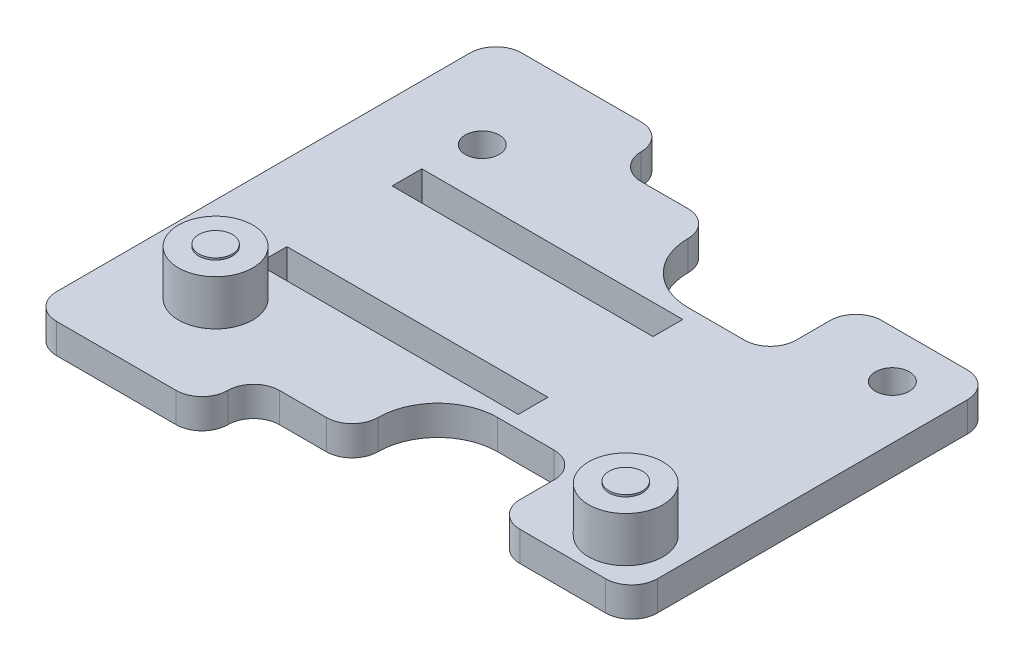
SolidWorks part; units mm, degrees
other "下垫片"
ref_plane "前视基准面" through (0, 0, 0) normal (0, 0, 1) x (1, 0, 0)
ref_plane "上视基准面" through (0, 0, 0) normal (0, 1, 0) x (1, 0, 0)
ref_plane "右视基准面" through (0, 0, 0) normal (1, 0, 0) x (0, 0, -1)
other "Configuration Table"
sketch "草图1" plane through (0, 0, 0) normal (0, 1, 0) x (1, 0, 0)
  line L0 (-89.3251, 0) -> (102.0425, 0) construction
  line L1 (0, 56.7239) -> (0, -62.578) construction
  line L2 (-33.2, -8.1375) -> (7.2, -8.1375)
  line L3 (-33.2, 12.7375) -> (7.2, 12.7375)
  line L4 (-33.2, 12.7375) -> (-33.2, 8.1375)
  line L5 (-33.2, 8.1375) -> (7.2, 8.1375)
  line L6 (7.2, 12.7375) -> (7.2, 8.1375)
  line L7 (-33.2, 12.7375) -> (7.2, 8.1375) construction
  line L8 (-33.2, 8.1375) -> (7.2, 12.7375) construction
  line L9 (7.2, -12.7375) -> (7.2, -8.1375)
  line L10 (-33.2, -12.7375) -> (7.2, -12.7375)
  line L11 (-33.2, -12.7375) -> (-33.2, -8.1375)
  line L14 (-3.25, -26.5375) -> (-3.25, -14.7375)
  line L15 (-3.25, -14.7375) -> (18.75, -14.7375)
  line L16 (18.75, -26.5375) -> (18.75, -14.7375)
  line L17 (-3.25, -26.5375) -> (18.75, -14.7375) construction
  line L18 (-3.25, -14.7375) -> (18.75, -26.5375) construction
  line L19 (-3.25, 14.7375) -> (18.75, 14.7375)
  line L20 (18.75, 26.5375) -> (18.75, 14.7375)
  line L22 (-3.25, 26.5375) -> (-3.25, 14.7375)
  line L23 (-3.25, 29.8695) -> (18.75, 29.8695)
  line L25 (-3.25, -26.5375) -> (-3.25, -29.8695)
  line L26 (-3.25, -29.8695) -> (18.75, -29.8695)
  line L27 (18.75, -26.5375) -> (18.75, -29.8695)
  line L28 (18.75, 26.5375) -> (18.75, 29.8695)
  line L30 (-3.25, 26.5375) -> (-3.25, 29.8695)
  circle A0 centre (-31.75, 20.6375) radius 2.625
  circle A4 centre (31.75, 20.6375) radius 2.625
  circle A5 centre (31.75, -20.6375) radius 2.625
  circle A6 centre (-31.75, -20.6375) radius 2.625
  point P13 (-13, 10.4375)
  point P22 (7.75, -20.6375)
  point P35 (-13, 10.4375)
  dimension "D5" = 5.25
  dimension "D11" = 5.25
  dimension "D1" = 40.4
  dimension "D2" = 31.75
  dimension "D3" = 4.6
  dimension "D4" = 20.6375
  dimension "D6" = 11.8
  dimension "D7" = 22
  dimension "D8" = 11.8
  dimension "D9" = 0
  dimension "D10" = 13
  dimension "D12" = 4.6
  dimension "D13" = 40.4
  dimension "D14" = 13
  dimension "D15" = 10.4375
  dimension "D16" = 2
sketch "草图3" plane through (0, 0, 0) normal (0, 1, 0) x (1, 0, 0)
  line L0 (-55, 0) -> (55, 0) construction
  line L1 (-18.5, -28) -> (40, -28)
  line L3 (-18.5, 28) -> (40, 28)
  line L4 (40, -28) -> (40, 28)
  line L5 (-40, -28) -> (40, 28) construction
  line L6 (-40, 28) -> (40, -28) construction
  line L10 (-45, 28) -> (-45, -28)
  line L12 (-45, -28) -> (-45, -36)
  line L13 (-45, -36) -> (-18.5, -36)
  line L14 (-18.5, -28) -> (-18.5, -36)
  line L15 (-18.5, 28) -> (-18.5, 36)
  line L16 (-45, 36) -> (-18.5, 36)
  line L17 (-45, 28) -> (-45, 36)
  point P0 (0, 0)
  dimension "D1" = 56
  dimension "D2" = 80
  dimension "D3" = 5
  dimension "D4" = 26.5
  dimension "D5" = 8
extrude "凸台-拉伸1" add sketch "草图3" along normal blind 4.6
extrude "切除-拉伸1" cut sketch "草图1" along normal up to surface (4.6 mm away) up to face at (-10.5, 4.6, 0)
sketch "草图5" plane through (0, 4.6, 0) normal (0, 1, 0) x (1, 0, 0)
  circle A0 centre (31.75, -20.6375) radius 5.75
  dimension "D1" = 11.5
extrude "凸台-拉伸2" add sketch "草图5" along normal blind 7
sketch "草图6" plane through (0, 11.6, 0) normal (0, 1, 0) x (1, 0, 0)
  circle A0 centre (31.75, -20.6375) radius 2.6
  dimension "D1" = 5.2
extrude "凸台-拉伸3" add sketch "草图6" along normal blind 0.3
fillet "圆角2" radius 4 14 edges at (-3.25, 2.3, -28) (18.75, 2.3, -28) (40, 2.3, -28) (40, 2.3, 28) (18.75, 2.3, 28) (-3.25, 2.3, 28) (18.75, 2.3, -14.7375) (18.75, 2.3, 14.7375) (-18.5, 2.3, 28) (-18.5, 2.3, 36) (-45, 2.3, 36) (-45, 2.3, -36) (-18.5, 2.3, -36) (-18.5, 2.3, -28)
mirror "镜向1" about plane through (0, 0, 0) normal (1, 0, 0) of "凸台-拉伸3", "凸台-拉伸2"
fillet "圆角3" radius 9.2625 2 edges at (-3.25, 2.3, -14.7375) (-3.25, 2.3, 14.7375)
